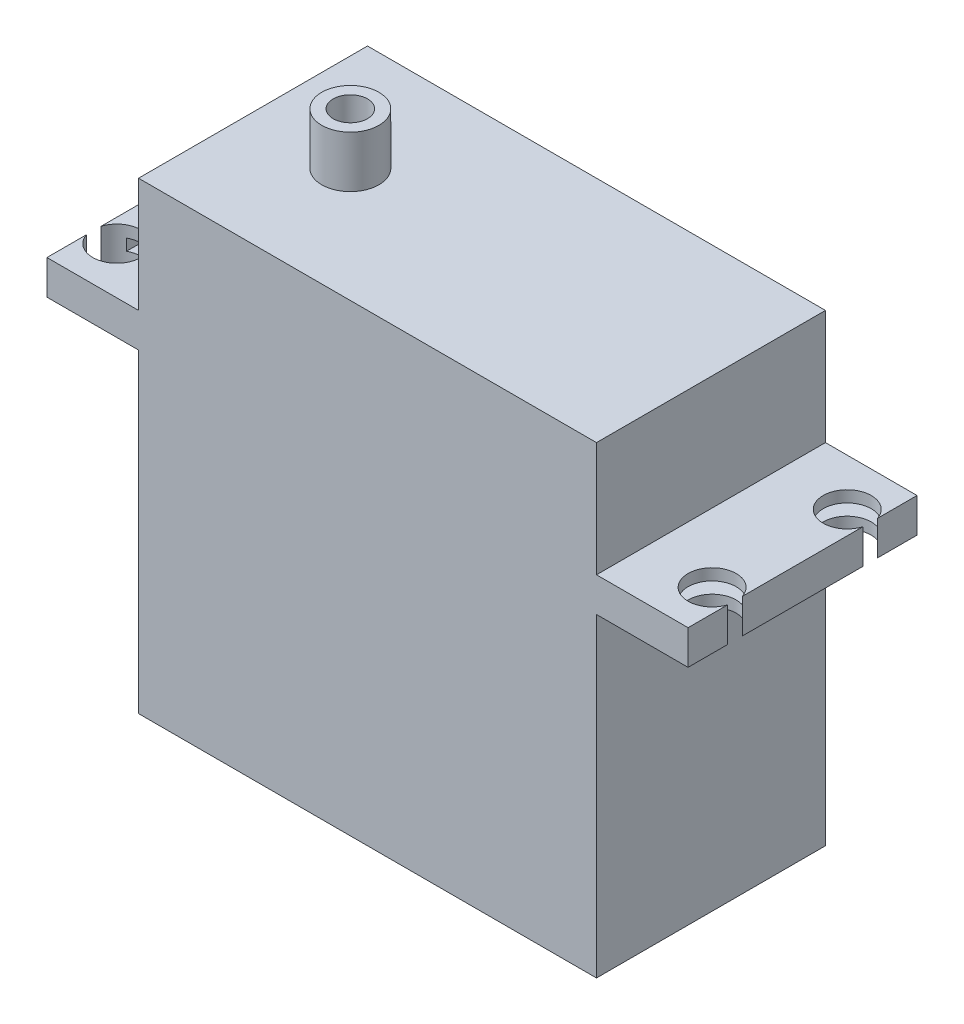
SolidWorks part; units mm, degrees
ref_plane "Front Plane" through (0, 0, 0) normal (0, 0, 1) x (1, 0, 0)
ref_plane "Top Plane" through (0, 0, 0) normal (0, 1, 0) x (1, 0, 0)
ref_plane "Right Plane" through (0, 0, 0) normal (1, 0, 0) x (0, 0, -1)
sketch "Sketch1" plane through (0, 0, 0) normal (0, 0, 1) x (1, 0, 0)
  line L0 (0, 0) -> (40, 0)
  line L1 (40, 0) -> (40, 40.5)
  line L2 (40, 40.5) -> (0, 40.5)
  line L3 (0, 40.5) -> (0, 0)
  dimension "D1" = 40
  dimension "D2" = 40.5
extrude "Boss-Extrude1" add sketch "Sketch1" against normal blind 10 and the other way blind 10
sketch "Sketch2" plane through (40, 0, 0) normal (1, 0, 0) x (0, 0, -1)
  line L1 (-10, 0) -> (-10, 40.5) construction
  line L2 (-10, 30.5) -> (10, 30.5)
  line L3 (10, 0) -> (10, 40.5) construction
  line L4 (10, 30.5) -> (10, 27.5)
  line L5 (10, 27.5) -> (-10, 27.5)
  line L6 (-10, 27.5) -> (-10, 30.5)
  dimension "D1" = 10
  dimension "D2" = 3
extrude "Boss-Extrude2" add sketch "Sketch2" along normal blind 8
sketch "Sketch3" plane through (0, 0, 0) normal (-1, 0, 0) x (0, 0, 1)
  line L0 (10, 30.5) -> (-10, 30.5)
  line L1 (10, 40.5) -> (10, 0) construction
  line L2 (-10, 30.5) -> (-10, 27.5)
  line L3 (-10, 27.5) -> (10, 27.5)
  line L4 (10, 27.5) -> (10, 30.5)
  dimension "D1" = 10
extrude "Boss-Extrude3" add sketch "Sketch3" along normal blind 8
sketch "Sketch4" plane through (0, 40.5, 0) normal (0, 1, 0) x (1, 0, 0)
  line L1 (40, -10) -> (0, -10) construction
  circle A0 centre (8.5, 0) radius 2.5
  dimension "D3" = 10
  dimension "D2" = 5
  dimension "D1" = 8.5
extrude "Boss-Extrude4" add sketch "Sketch4" along normal blind 4.5
shell "Shell1" thickness 1 removed face at (6, 45, 0)
sketch "Sketch5" plane through (0, 30.5, 0) normal (0, 1, 0) x (1, 0, 0)
  line L0 (-8, 10) -> (0, 10) construction
  line L2 (0, -10) -> (0, 10) construction
  line L3 (-8, -10) -> (0, -10) construction
  circle A0 centre (-6, 5.9) radius 2.1
  circle A1 centre (-6, -5.9) radius 2.1
  dimension "D2" = 4.2
  dimension "D1" = 4.1
  dimension "D4" = 4.2
  dimension "D3" = 6
  dimension "D5" = 4.1
  dimension "D6" = 6
extrude "Cut-Extrude1" cut sketch "Sketch5" against normal blind 10
sketch "Sketch6" plane through (0, 30.5, 0) normal (0, 1, 0) x (1, 0, 0)
  line L0 (40, 10) -> (40, -10) construction
  line L1 (48, 10) -> (40, 10) construction
  line L2 (48, -10) -> (40, -10) construction
  circle A0 centre (46, 5.9) radius 2.1
  circle A2 centre (46, -5.9) radius 2.1
  dimension "D1" = 4.2
  dimension "D4" = 4.2
  dimension "D2" = 6
  dimension "D3" = 4.1
  dimension "D5" = 4.1
  dimension "D6" = 6
extrude "Cut-Extrude2" cut sketch "Sketch6" against normal blind 10
